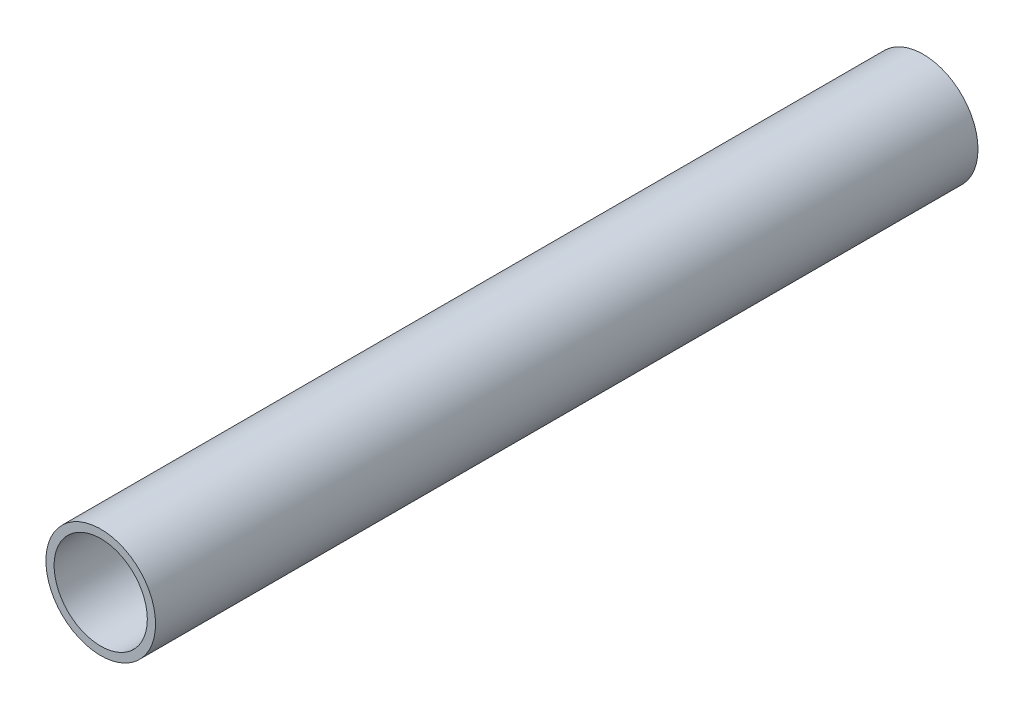
SolidWorks part; units mm, degrees
ref_plane "Front Plane" through (0, 0, 0) normal (0, 0, 1) x (1, 0, 0)
ref_plane "Top Plane" through (0, 0, 0) normal (0, 1, 0) x (1, 0, 0)
ref_plane "Right Plane" through (0, 0, 0) normal (1, 0, 0) x (0, 0, -1)
sketch "Sketch1" plane through (0, 0, 0) normal (0, 0, 1) x (1, 0, 0)
  circle A0 centre (0, 0) radius 20
  circle A1 centre (0, 0) radius 17
  dimension "D1" = 40
  dimension "D2" = 34
extrude "Boss-Extrude1" add sketch "Sketch1" along normal blind 300
sketch "Sketch2" [suppressed] plane through (0, 0, 0) normal (1, 0, 0) x (0, -1, 0)
  line L0 (0, 0) -> (0, -300) construction
  line L1 (-20, -300) -> (20, -300) construction
  line L3 (-10, -255) -> (10, -255)
  line L4 (-10, -255) -> (-10, -247)
  line L5 (-10, -247) -> (10, -247)
  line L6 (10, -255) -> (10, -247)
  line L7 (-10, -255) -> (10, -247) construction
  line L8 (-10, -247) -> (10, -255) construction
  point P5 (0, -251)
  dimension "D1" = 20
  dimension "D2" = 8
  dimension "D3" = 42
extrude "Cut-Extrude1" [suppressed] cut sketch "Sketch2" against normal through all
